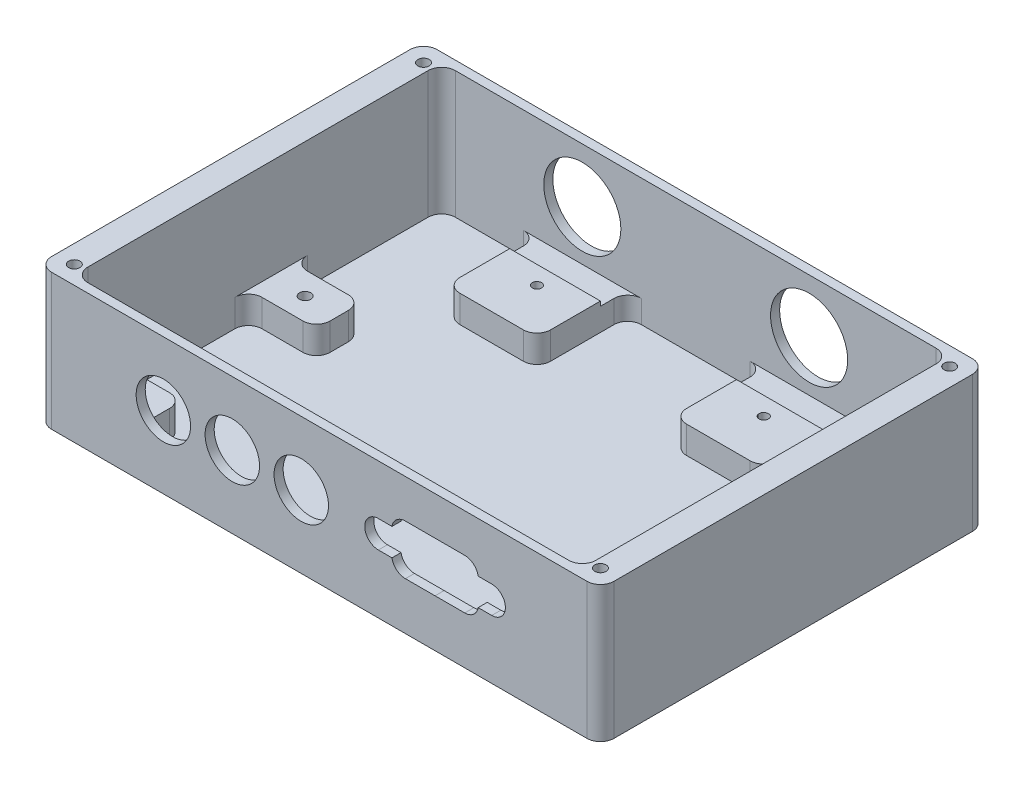
SolidWorks part; units mm, degrees
ref_plane "Ebene vorne" through (0, 0, 0) normal (0, 0, 1) x (1, 0, 0)
ref_plane "Ebene oben" through (0, 0, 0) normal (0, 1, 0) x (1, 0, 0)
ref_plane "Ebene rechts" through (0, 0, 0) normal (1, 0, 0) x (0, 0, -1)
sketch "Skizze1" plane through (0, 0, 0) normal (0, 1, 0) x (1, 0, 0)
  line L1 (0, 0) -> (116, 0)
  line L2 (0, 0) -> (0, 85)
  line L3 (0, 85) -> (116, 85)
  line L4 (116, 0) -> (116, 85)
  dimension "D1" = 85
  dimension "D2" = 116
extrude "Aufsatz-Linear austragen1" add sketch "Skizze1" along normal blind 30
shell "Schale1" thickness 2 removed face at (58, 30, -42.5)
sketch "Skizze2" plane through (0, 0, 0) normal (0, 0, 1) x (1, 0, 0)
  line L0 (4.8493, 15.94) -> (121.4088, 15.94) construction
  line L1 (0, 0) -> (116, 0) construction
  line L2 (0, 30) -> (0, 0) construction
  circle A0 centre (23.64, 15.94) radius 6
  circle A1 centre (38.84, 15.94) radius 6
  circle A2 centre (54.04, 15.94) radius 6
  dimension "D2" = 12
  dimension "D3" = 23.64
  dimension "D4" = 38.84
  dimension "D5" = 54.04
  dimension "D8" = 12
  dimension "D9" = 12
  dimension "D1" = 15.94
extrude "Schnitt-Linear austragen1" cut sketch "Skizze2" against normal blind 30
sketch "Skizze3" plane through (0, 0, 0) normal (0, 0, 1) x (1, 0, 0)
  line L0 (83.5402, 21.49) -> (76.9981, 21.49)
  line L1 (74.0401, 18.99) -> (71.04, 18.99)
  line L2 (0, 30) -> (0, 0) construction
  line L3 (68.04, 15.99) -> (134.747, 15.99) construction
  line L5 (83.5399, 11.9127) -> (83.5402, 21.49) construction
  line L7 (83.5402, 10.49) -> (76.9981, 10.49)
  line L8 (74.0401, 12.99) -> (71.04, 12.99)
  line L9 (83.5395, 10.49) -> (90.0816, 10.4896)
  line L10 (83.5402, 21.49) -> (90.0822, 21.4896)
  line L11 (93.0398, 12.9895) -> (96.0398, 12.9893)
  line L12 (93.0401, 18.9895) -> (96.0402, 18.9893)
  arc A0 (76.9981, 21.49) -> (74.0401, 18.99) centre (76.9981, 18.49) ccw
  arc A1 (71.04, 18.99) -> (71.04, 12.99) centre (71.04, 15.99) ccw
  arc A2 (76.9981, 10.49) -> (74.0401, 12.99) centre (76.9981, 13.49) cw
  arc A3 (90.0816, 10.4896) -> (93.0398, 12.9895) centre (90.0817, 13.4896) ccw
  arc A4 (96.0402, 18.9893) -> (96.0398, 12.9893) centre (96.04, 15.9893) cw
  arc A5 (90.0822, 21.4896) -> (93.0401, 18.9895) centre (90.082, 18.4896) cw
  point P12 (68.04, 15.99)
  dimension "D7" = 3
  dimension "D1" = 5.5
  dimension "D2" = 9.5
  dimension "D3" = 3
  dimension "D4" = 15.99
  dimension "D5" = 68.04
  dimension "D6" = 15.5
extrude "Schnitt-Linear austragen2" cut sketch "Skizze3" against normal blind 10 contours A5 L10 L0 A0 L1 A1 L8 A2 L7 L9 A3 L11 A4 L12 region at (83.54, 15.9898, 0)
fillet "Verrundung1" radius 3 8 edges at (0, 15, -85) (116, 15, -85) (116, 15, 0) (0, 15, 0) (114, 16, -2) (114, 16, -83) (2, 16, -83) (2, 16, -2)
sketch "Skizze4" plane through (0, 2, 0) normal (0, 1, 0) x (1, 0, 0)
  line L0 (2, 12) -> (13, 12)
  line L1 (2, 80) -> (2, 5) construction
  line L2 (16, 9) -> (16, 2)
  line L3 (5, 2) -> (111, 2) construction
  line L5 (5, 2) -> (16, 2)
  line L6 (2, 12) -> (2, 5)
  line L7 (58, 0) -> (58, 20.7722) construction
  line L8 (3, 0) -> (113, 0) construction
  line L9 (114, 12) -> (114, 5)
  line L10 (111, 2) -> (100, 2)
  line L11 (100, 9) -> (100, 2)
  line L12 (114, 12) -> (103, 12)
  arc A1 (13, 12) -> (16, 9) centre (13, 9) cw
  arc A2 (2, 5) -> (5, 2) centre (5, 5) ccw construction
  arc A3 (2, 5) -> (5, 2) centre (5, 5) ccw
  arc A4 (114, 5) -> (111, 2) centre (111, 5) cw
  arc A5 (103, 12) -> (100, 9) centre (103, 9) ccw
  point P13 (16, 12)
  line M4 (5, 2) -> (111, 2)
  arc M5 (111, 2) -> (114, 5) centre (111, 5) ccw
  line M6 (114, 5) -> (114, 80)
  line M10 (2, 80) -> (2, 5)
  arc M11 (2, 5) -> (5, 2) centre (5, 5) ccw
  dimension "D5" = 3
  dimension "D3" = 14
  dimension "D4" = 10
extrude "Aufsatz-Linear austragen2" add sketch "Skizze4" along normal blind 6 contours A1 L0 L2 M10 M11 M4 | L12 A5 L11 M4 M5 M6 region at (107, 2, -7) region at (9, 2, -7)
fillet "Verrundung2" radius 3 4 edges at (114, 5, -12) (100, 5, -2) (16, 5, -2) (2, 5, -12)
sketch "Skizze5" plane through (0, 2, 0) normal (0, 1, 0) x (1, 0, 0)
  line L0 (2, 80) -> (2, 5) construction
  line L1 (2, 50.4) -> (17, 50.4)
  line L2 (2, 50.4) -> (2, 40.4)
  line L3 (2, 40.4) -> (17, 40.4)
  line L4 (17, 50.4) -> (17, 40.4)
  line L5 (16, 7) -> (7.9271, 7) construction
  line L6 (16, 9) -> (16, 5) construction
  line L7 (17, 45.4) -> (7.9271, 45.4) construction
  line L8 (58, 0) -> (58, 60.7015) construction
  line L9 (3, 0) -> (113, 0) construction
  line L10 (99, 50.4) -> (99, 40.4)
  line L11 (114, 40.4) -> (99, 40.4)
  line L12 (114, 50.4) -> (114, 40.4)
  line L13 (114, 50.4) -> (99, 50.4)
  dimension "D1" = 38.4
  dimension "D2" = 10
  dimension "D3" = 15
extrude "Aufsatz-Linear austragen3" add sketch "Skizze5" along normal blind 6
fillet "Verrundung3" radius 3 8 edges at (114, 5, -40.4) (114, 5, -50.4) (99, 5, -40.4) (99, 5, -50.4) (2, 5, -50.4) (17, 5, -50.4) (17, 5, -40.4) (2, 5, -40.4)
sketch "Skizze6" plane through (0, 0, -85) normal (0, 0, -1) x (-1, 0, 0)
  line L0 (-128.5127, 18) -> (-8.2871, 18) construction
  line L1 (-113, 0) -> (-3, 0) construction
  line L2 (-58, 0) -> (-58, 33.8667) construction
  circle A0 centre (-83, 18) radius 8.5
  circle A1 centre (-33, 18) radius 8.5
  dimension "D2" = 17
  dimension "D3" = 50
  dimension "D1" = 18
extrude "Schnitt-Linear austragen3" cut sketch "Skizze6" against normal blind 5
sketch "Skizze7" plane through (0, 2, 0) normal (0, 1, 0) x (1, 0, 0)
  line L0 (58, 85) -> (58, 35.1088) construction
  line L1 (113, 85) -> (3, 85) construction
  line L2 (111, 83) -> (5, 83) construction
  line L3 (23, 63) -> (43, 63)
  line L4 (23, 63) -> (23, 83)
  line L5 (23, 83) -> (43, 83)
  line L6 (43, 63) -> (43, 83)
  line L7 (33, 63) -> (33, 71.5986) construction
  line L8 (0, 82) -> (0, 3) construction
  line L9 (23, 63) -> (23, 83)
  line L10 (43, 63) -> (43, 83)
  line L11 (93, 83) -> (73, 83)
  line L12 (73, 63) -> (73, 83)
  line L13 (93, 63) -> (73, 63)
  line L14 (93, 63) -> (93, 83)
  line M17 (111, 83) -> (5, 83)
  dimension "D1" = 33
  dimension "D2" = 20
  dimension "D3" = 20
extrude "Aufsatz-Linear austragen4" add sketch "Skizze7" along normal blind 6 contours L3 L6 L4 M17 | L13 L14 L12 M17 region at (33, 2, -73) region at (83, 2, -73)
fillet "Verrundung4" radius 3 8 edges at (93, 5, -83) (93, 5, -63) (73, 5, -63) (73, 5, -83) (23, 5, -83) (23, 5, -63) (43, 5, -83) (43, 5, -63)
hole_wizard "M3 Gewindebohrung1" positions "Skizze8" profile "Skizze9" tap size "M3" standard "DIN"
sketch "Skizze8" plane through (0, 8, 0) normal (0, 1, 0) x (1, 0, 0)
  line L1 (106.5, 7.4) -> (9.5, 7.4) construction
  line L2 (106.5, 7.4) -> (106.5, 45.4) construction
  line L3 (106.5, 45.4) -> (9.5, 45.4) construction
  line L4 (9.5, 7.4) -> (9.5, 45.4) construction
  line L5 (19, 2) -> (97, 2) construction
  line L6 (114, 15) -> (114, 37.4) construction
  line L7 (58, 0) -> (58, 59.3993) construction
  line L8 (3, 0) -> (113, 0) construction
  point P1 (106.5, 7.4)
  point P2 (9.5, 45.4)
  point P117 (106.5, 45.4)
  point P118 (9.5, 7.4)
  dimension "D1" = 5.4
  dimension "D2" = 7.5
  dimension "D3" = 38
  dimension "D4" = 97
sketch "Skizze9" plane through (106.5, 8, -7.4) normal (1, 0, 0) x (0, 0, 1)
  line L0 (0, 0) -> (0, 9.2511)
  line L1 (0, 9.2511) -> (1.25, 8.5)
  line L2 (1.25, 8.5) -> (1.25, 0)
  line L5 (1.25, 0) -> (0, 0)
  line L10 (0, 9.2511) -> (-1.25, 8.5) construction
  line L11 (0, -6.35) -> (0, 107.95) construction
  dimension "Bohrerdurchmesser" = 2.5
  dimension "Bohrungstiefe" = 8.5
  dimension "Spitzenwinkel" = 118
cosmetic thread "Bohrungsgewinde4" parameters "D1"=6, "D2"=3
cosmetic thread "Bohrungsgewinde7" parameters "D1"=6, "D2"=3
cosmetic thread "Bohrungsgewinde9" parameters "D1"=6, "D2"=3
cosmetic thread "Bohrungsgewinde10" parameters "D1"=6, "D2"=3
hole_wizard "M2.5 Gewindebohrung1" positions "Skizze10" profile "Skizze11" tap size "M2.5" standard "DIN" end condition through all
sketch "Skizze10" plane through (0, 8, 0) normal (0, 1, 0) x (1, 0, 0)
  line L0 (83, 63) -> (83, 83) construction
  line L1 (90, 63) -> (76, 63) construction
  line L2 (33, 63) -> (33, 83) construction
  line L3 (26, 63) -> (40, 63) construction
  line L4 (96, 83) -> (70, 83) construction
  point P10 (83, 73)
  point P12 (33, 73)
  dimension "D1" = 10
cosmetic thread "Bohrungsgewinde5" parameters "D2"=2.5
cosmetic thread "Bohrungsgewinde6" parameters "D2"=2.5
sketch "Skizze11" plane through (33, 8, -73) normal (1, 0, 0) x (0, 0, 1)
  line L0 (0, 0) -> (0, 8)
  line L1 (0, 8) -> (1.025, 8)
  line L2 (1.025, 8) -> (1.025, 0)
  line L5 (1.025, 0) -> (0, 0)
  line L11 (0, -6.35) -> (0, 107.95) construction
  dimension "Bohrerdurchmesser" = 2.05
  dimension "Bohrungstiefe" = 8
sketch "Skizze12" plane through (0, 8, 0) normal (0, 1, 0) x (1, 0, 0)
  line L0 (111, 83) -> (96, 83) construction
  line L1 (108.8489, 83) -> (18.8489, 83)
  line L2 (108.8489, 83) -> (108.8489, 77)
  line L3 (108.8489, 77) -> (18.8489, 77)
  line L4 (18.8489, 83) -> (18.8489, 77)
  dimension "D1" = 6
  dimension "D2" = 90
extrude "Schnitt-Linear austragen4" cut sketch "Skizze12" against normal blind 1
sketch "Skizze13" plane through (0, 2, 0) normal (0, 1, 0) x (1, 0, 0)
  line L0 (119.1739, 25) -> (-5.709, 25) construction
  line L1 (58, 0) -> (58, 42.5667) construction
  line L2 (3, 0) -> (113, 0) construction
  circle A0 centre (88, 25) radius 3.2
  circle A1 centre (28, 25) radius 3.2
  dimension "D2" = 6.4
  dimension "D3" = 30
  dimension "D1" = 25
extrude "Schnitt-Linear austragen5" cut sketch "Skizze13" against normal blind 10
sketch "Skizze14" plane through (0, 0, 0) normal (0, -1, 0) x (-1, 0, 0)
  line L0 (-116, 3) -> (-116, 82) construction
  line L1 (-116, 0) -> (-120, 0)
  line L2 (-116, 3) -> (-116, 82)
  line L3 (-116, 85) -> (-120, 85)
  line L4 (-120, 0) -> (-120, 85)
  line L5 (0, 85) -> (4, 85)
  line L6 (0, 82) -> (0, 3)
  line L7 (0, 0) -> (4, 0)
  line L8 (4, 85) -> (4, 0)
  line L9 (0, 82) -> (0, 3) construction
  line L10 (-113, 85) -> (-116, 85)
  line L11 (-113, 0) -> (-116, 0)
  line L12 (-3, 0) -> (-113, 0) construction
  line L13 (0, 85) -> (-3, 85)
  line L14 (0, 0) -> (-3, 0)
  arc A0 (-113, 85) -> (-116, 82) centre (-113, 82) ccw
  arc A1 (-116, 3) -> (-113, 0) centre (-113, 3) ccw
  arc A2 (-3, 0) -> (0, 3) centre (-3, 3) ccw
  arc A3 (-3, 0) -> (0, 3) centre (-3, 3) ccw construction
  arc A4 (-3, 85) -> (0, 82) centre (-3, 82) cw
  arc A5 (0, 82) -> (-3, 85) centre (-3, 82) ccw construction
  dimension "D1" = 4
  dimension "D2" = 4
extrude "Aufsatz-Linear austragen5" add sketch "Skizze14" against normal up to surface (30 mm away) up to face at (58, 30, -42.5)
fillet "Verrundung5" radius 3 4 edges at (-4, 15, -85) (-4, 15, 0) (120, 15, -85) (120, 15, 0)
hole_wizard "M3 Gewindebohrung2" positions "Skizze15" profile "Skizze16" tap size "M3" standard "DIN"
sketch "Skizze15" plane through (0, 30, 0) normal (0, 1, 0) x (1, 0, 0)
  line L1 (0, 4) -> (116, 4) construction
  line L2 (0, 4) -> (0, 81) construction
  line L3 (0, 81) -> (116, 81) construction
  line L4 (116, 4) -> (116, 81) construction
  line L5 (117, 85) -> (-1, 85) construction
  line L6 (-1, 0) -> (117, 0) construction
  line L7 (120, 3) -> (120, 82) construction
  line L8 (-4, 82) -> (-4, 3) construction
  point P0 (0, 4)
  point P1 (116, 81)
  point P106 (0, 81)
  point P107 (116, 4)
  dimension "D1" = 4
  dimension "D2" = 4
  dimension "D3" = 4
  dimension "D4" = 4
sketch "Skizze16" plane through (0, 30, -4) normal (1, 0, 0) x (0, 0, 1)
  line L0 (0, 0) -> (0, 9.2511)
  line L1 (0, 9.2511) -> (1.25, 8.5)
  line L2 (1.25, 8.5) -> (1.25, 0)
  line L5 (1.25, 0) -> (0, 0)
  line L10 (0, 9.2511) -> (-1.25, 8.5) construction
  line L11 (0, -6.35) -> (0, 107.95) construction
  dimension "Bohrerdurchmesser" = 2.5
  dimension "Bohrungstiefe" = 8.5
  dimension "Spitzenwinkel" = 118
cosmetic thread "Bohrungsgewinde11" parameters "D1"=6, "D2"=3
cosmetic thread "Bohrungsgewinde12" parameters "D1"=6, "D2"=3
cosmetic thread "Bohrungsgewinde13" parameters "D1"=6, "D2"=3
cosmetic thread "Bohrungsgewinde14" parameters "D1"=6, "D2"=3
